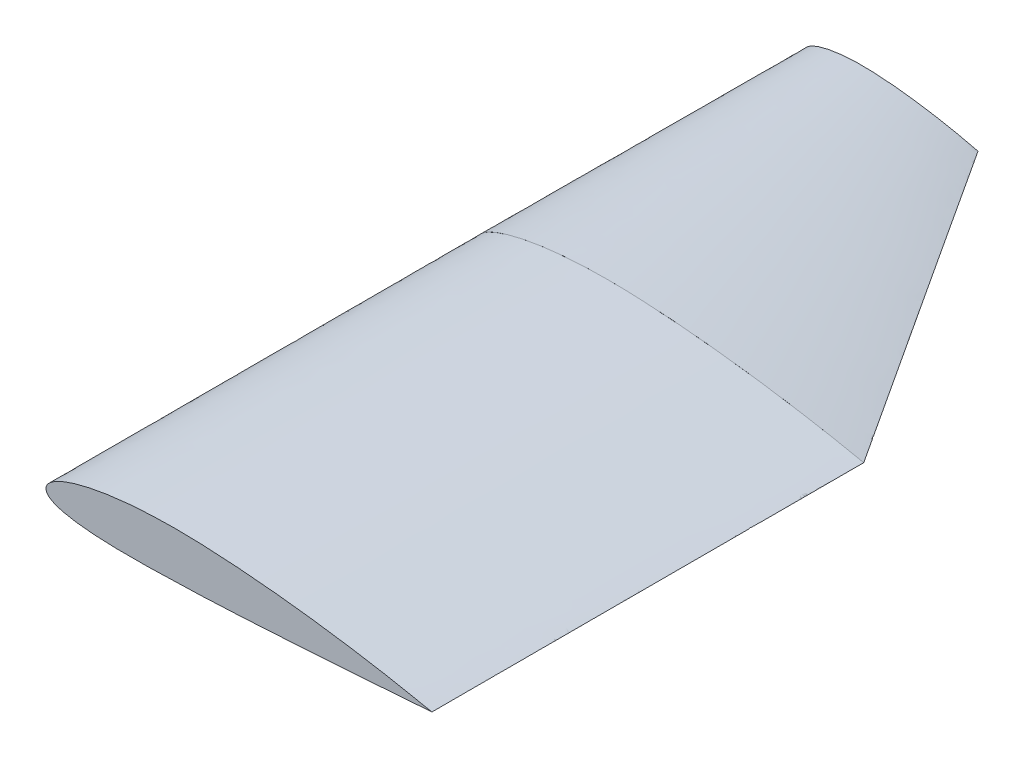
SolidWorks part; units mm, degrees
ref_plane "Front Plane" through (0, 0, 0) normal (0, 0, 1) x (1, 0, 0)
ref_plane "Top Plane" through (0, 0, 0) normal (0, 1, 0) x (1, 0, 0)
ref_plane "Right Plane" through (0, 0, 0) normal (1, 0, 0) x (0, 0, -1)
curve "Airfoil_curve"
  spline degree 3 poles (411.7817, -0.0157, 0) (412.0536, -0.0023, 0) (411.7836, 0.0347, 0) (411.5641, 0.1099, 0) (411.0101, 0.1971, 0) (410.3301, 0.3578, 0) (409.4199, 0.5405, 0) (408.326, 0.7892, 0) (407.0216, 1.0497, 0) (405.5282, 1.3771, 0) (403.8332, 1.7229, 0) (401.9465, 2.1127, 0) (399.8677, 2.5449, 0) (397.6006, 3.0028, 0) (395.1434, 3.4936, 0) (392.5025, 4.019, 0) (389.6787, 4.5968, 0) (386.6746, 5.1833, 0) (383.4891, 5.7888, 0) (380.1348, 6.4442, 0) (376.6043, 7.112, 0) (372.9076, 7.802, 0) (369.0432, 8.5093, 0) (365.0217, 9.2525, 0) (360.8384, 10.0029, 0) (356.5035, 10.7574, 0) (352.0215, 11.542, 0) (347.3944, 12.3298, 0) (342.6243, 13.1292, 0) (337.7185, 13.9416, 0) (332.6805, 14.7465, 0) (327.5183, 15.5701, 0) (322.2356, 16.3914, 0) (316.8334, 17.1938, 0) (311.3256, 18.0218, 0) (305.7074, 18.8254, 0) (299.9917, 19.6385, 0) (294.1815, 20.4376, 0) (288.2846, 21.2259, 0) (282.3022, 22.0103, 0) (276.241, 22.7644, 0) (270.1077, 23.515, 0) (263.9155, 24.2589, 0) (257.6615, 24.9669, 0) (251.3539, 25.6518, 0) (244.9992, 26.3415, 0) (238.601, 26.9733, 0) (232.171, 27.5935, 0) (225.7154, 28.2001, 0) (219.2373, 28.7506, 0) (212.7452, 29.2999, 0) (206.2443, 29.7927, 0) (199.7414, 30.2674, 0) (193.2446, 30.6967, 0) (186.7574, 31.0835, 0) (180.2877, 31.4458, 0) (173.8445, 31.7696, 0) (167.4205, 32.031, 0) (161.0179, 32.2854, 0) (154.6405, 32.4451, 0) (148.3071, 32.5705, 0) (142.0301, 32.6306, 0) (135.8166, 32.6263, 0) (129.6728, 32.5849, 0) (123.6061, 32.4571, 0) (117.6223, 32.2925, 0) (111.7252, 32.0621, 0) (105.9252, 31.7702, 0) (100.2245, 31.434, 0) (94.634, 31.0345, 0) (89.1574, 30.5729, 0) (83.8002, 30.0647, 0) (78.5697, 29.5053, 0) (73.4693, 28.8957, 0) (68.5018, 28.2383, 0) (63.6755, 27.5262, 0) (58.9936, 26.7811, 0) (54.4673, 25.9796, 0) (50.0931, 25.1409, 0) (45.88, 24.2608, 0) (41.8276, 23.3555, 0) (37.9479, 22.4045, 0) (34.2417, 21.424, 0) (30.7038, 20.43, 0) (27.352, 19.3887, 0) (24.1794, 18.3333, 0) (21.1983, 17.248, 0) (18.3933, 16.1691, 0) (15.7911, 15.0448, 0) (13.3707, 13.93, 0) (11.152, 12.7922, 0) (9.1264, 11.6418, 0) (7.297, 10.4891, 0) (5.6707, 9.3274, 0) (4.2399, 8.1698, 0) (3.0185, 7.0028, 0) (1.992, 5.8375, 0) (1.1752, 4.6687, 0) (0.563, 3.4965, 0) (0.151, 2.3287, 0) (-0.0419, 1.1579, 0) (-0.0371, -0.0042, 0) (0.1915, -1.1429, 0) (0.607, -2.2544, 0) (1.2396, -3.3208, 0) (2.0755, -4.3427, 0) (3.0896, -5.3391, 0) (4.3178, -6.2756, 0) (5.7295, -7.1839, 0) (7.3412, -8.0509, 0) (9.1362, -8.8886, 0) (11.1275, -9.6726, 0) (13.2979, -10.4337, 0) (15.6581, -11.1486, 0) (18.197, -11.8252, 0) (20.9146, -12.4663, 0) (23.81, -13.0612, 0) (26.8808, -13.6211, 0) (30.1228, -14.1355, 0) (33.5284, -14.6301, 0) (37.1001, -15.0653, 0) (40.8312, -15.4611, 0) (44.7171, -15.8372, 0) (48.762, -16.1485, 0) (52.9517, -16.4426, 0) (57.2891, -16.6865, 0) (61.762, -16.9145, 0) (66.3764, -17.0724, 0) (71.1193, -17.2298, 0) (75.993, -17.3388, 0) (80.9899, -17.4016, 0) (86.1065, -17.459, 0) (91.3367, -17.4646, 0) (96.6734, -17.4422, 0) (102.1135, -17.4051, 0) (107.6536, -17.3344, 0) (113.2902, -17.2328, 0) (119.0167, -17.1091, 0) (124.8271, -16.9857, 0) (130.7136, -16.8221, 0) (136.6734, -16.6394, 0) (142.7003, -16.4538, 0) (148.7901, -16.2395, 0) (154.9369, -16.0221, 0) (161.1399, -15.7864, 0) (167.4073, -15.5657, 0) (173.7271, -15.3028, 0) (180.0935, -15.0195, 0) (186.4839, -14.7345, 0) (192.8969, -14.4205, 0) (199.3235, -14.1009, 0) (205.7606, -13.7742, 0) (212.197, -13.422, 0) (218.6266, -13.0592, 0) (225.047, -12.7027, 0) (231.4503, -12.3319, 0) (237.8305, -11.9545, 0) (244.1795, -11.5556, 0) (250.4943, -11.189, 0) (256.7663, -10.7768, 0) (262.9901, -10.3923, 0) (269.1639, -10.0047, 0) (275.2731, -9.5993, 0) (281.3169, -9.2129, 0) (287.2869, -8.823, 0) (293.1797, -8.4293, 0) (298.9907, -8.0571, 0) (304.7065, -7.6606, 0) (310.3298, -7.2807, 0) (315.8504, -6.9156, 0) (321.2664, -6.54, 0) (326.5671, -6.186, 0) (331.7532, -5.8214, 0) (336.8133, -5.4725, 0) (341.7504, -5.1361, 0) (346.5495, -4.7894, 0) (351.2138, -4.4768, 0) (355.7333, -4.1526, 0) (360.1067, -3.8433, 0) (364.3305, -3.5473, 0) (368.3962, -3.2406, 0) (372.3035, -2.9653, 0) (376.0434, -2.6944, 0) (379.6167, -2.4337, 0) (383.0202, -2.1862, 0) (386.2496, -1.9409, 0) (389.2974, -1.7296, 0) (392.163, -1.5022, 0) (394.8463, -1.3021, 0) (397.3441, -1.1302, 0) (399.6496, -0.9413, 0) (401.7637, -0.7874, 0) (403.6831, -0.6345, 0) (405.403, -0.5019, 0) (406.9273, -0.4009, 0) (408.25, -0.2803, 0) (409.3715, -0.2065, 0) (410.2993, -0.1365, 0) (410.9956, -0.0759, 0) (411.5538, -0.0325, 0) (411.7817, -0.0157, 0) (412.0536, -0.0023, 0) (411.7836, 0.0347, 0) knots -0.001097 -0.000489 -0.000119 0 0.000121 0.000487 0.001105 0.001956 0.00305 0.004388 0.005967 0.00779 0.009842 0.012136 0.014661 0.017415 0.020385 0.023598 0.027019 0.030665 0.034515 0.038583 0.042855 0.047329 0.051995 0.056866 0.061915 0.067153 0.072559 0.078143 0.083893 0.089809 0.095878 0.102089 0.108454 0.114945 0.121568 0.128318 0.135186 0.142159 0.149235 0.156405 0.163678 0.17102 0.178443 0.185921 0.193467 0.201071 0.208718 0.216398 0.224111 0.231843 0.239585 0.247348 0.255095 0.26284 0.270569 0.278273 0.28595 0.293578 0.301204 0.308803 0.31633 0.323796 0.331191 0.33849 0.345708 0.352832 0.35984 0.366756 0.373544 0.380207 0.386745 0.393146 0.399399 0.405505 0.411465 0.417269 0.422904 0.428373 0.433663 0.438788 0.443723 0.448472 0.453034 0.457396 0.461577 0.465551 0.469319 0.472891 0.476268 0.479427 0.482394 0.485157 0.487733 0.490102 0.492282 0.494291 0.49612 0.497812 0.499364 0.500823 0.502209 0.503576 0.504945 0.506329 0.507789 0.509345 0.511026 0.512848 0.514843 0.517008 0.51937 0.521904 0.524637 0.527571 0.530697 0.534007 0.537528 0.541238 0.545139 0.549235 0.553511 0.557971 0.562616 0.567434 0.572439 0.577596 0.582928 0.588412 0.594062 0.599853 0.605798 0.611885 0.618103 0.624451 0.630919 0.637506 0.644212 0.651025 0.657934 0.664939 0.672028 0.6792 0.686445 0.693761 0.701137 0.708584 0.716128 0.723696 0.731312 0.738942 0.746596 0.754262 0.761929 0.769585 0.77723 0.784863 0.792461 0.800025 0.807552 0.815021 0.822442 0.829792 0.837083 0.844279 0.851391 0.858421 0.865343 0.872159 0.878855 0.885444 0.891891 0.898218 0.904391 0.910433 0.916308 0.922041 0.927594 0.932981 0.938201 0.943231 0.948082 0.952743 0.957201 0.961456 0.965521 0.969371 0.973007 0.976417 0.979624 0.982604 0.985346 0.987874 0.990163 0.992214 0.994026 0.995612 0.996947 0.998044 0.998903 0.999511 0.999881 1 1.000121 1.000487 1.001105 periodic
ref_plane "Panel break" through (0, 0, 461) normal (0, 0, 1) x (1, 0, 0)
sketch "panel 1 root " plane through (0, 0, 0) normal (0, 0, 1) x (1, 0, 0)
  spline S0 degree 3 poles (411.7817, -0.0157) (412.0536, -0.0023) (411.7836, 0.0347) (411.5641, 0.1099) (411.0101, 0.1971) (410.3301, 0.3578) (409.4199, 0.5405) (408.326, 0.7892) (407.0216, 1.0497) (405.5282, 1.3771) (403.8332, 1.7229) (401.9465, 2.1127) (399.8677, 2.5449) (397.6006, 3.0028) (395.1434, 3.4936) (392.5025, 4.019) (389.6787, 4.5968) (386.6746, 5.1833) (383.4891, 5.7888) (380.1348, 6.4442) (376.6043, 7.112) (372.9076, 7.802) (369.0432, 8.5093) (365.0217, 9.2525) (360.8384, 10.0029) (356.5035, 10.7574) (352.0215, 11.542) (347.3944, 12.3298) (342.6243, 13.1292) (337.7185, 13.9416) (332.6805, 14.7465) (327.5183, 15.5701) (322.2356, 16.3914) (316.8334, 17.1938) (311.3256, 18.0218) (305.7074, 18.8254) (299.9917, 19.6385) (294.1815, 20.4376) (288.2846, 21.2259) (282.3022, 22.0103) (276.241, 22.7644) (270.1077, 23.515) (263.9155, 24.2589) (257.6615, 24.9669) (251.3539, 25.6518) (244.9992, 26.3415) (238.601, 26.9733) (232.171, 27.5935) (225.7154, 28.2001) (219.2373, 28.7506) (212.7452, 29.2999) (206.2443, 29.7927) (199.7414, 30.2674) (193.2446, 30.6967) (186.7574, 31.0835) (180.2877, 31.4458) (173.8445, 31.7696) (167.4205, 32.031) (161.0179, 32.2854) (154.6405, 32.4451) (148.3071, 32.5705) (142.0301, 32.6306) (135.8166, 32.6263) (129.6728, 32.5849) (123.6061, 32.4571) (117.6223, 32.2925) (111.7252, 32.0621) (105.9252, 31.7702) (100.2245, 31.434) (94.634, 31.0345) (89.1574, 30.5729) (83.8002, 30.0647) (78.5697, 29.5053) (73.4693, 28.8957) (68.5018, 28.2383) (63.6755, 27.5262) (58.9936, 26.7811) (54.4673, 25.9796) (50.0931, 25.1409) (45.88, 24.2608) (41.8276, 23.3555) (37.9479, 22.4045) (34.2417, 21.424) (30.7038, 20.43) (27.352, 19.3887) (24.1794, 18.3333) (21.1983, 17.248) (18.3933, 16.1691) (15.7911, 15.0448) (13.3707, 13.93) (11.152, 12.7922) (9.1264, 11.6418) (7.297, 10.4891) (5.6707, 9.3274) (4.2399, 8.1698) (3.0185, 7.0028) (1.992, 5.8375) (1.1752, 4.6687) (0.563, 3.4965) (0.151, 2.3287) (-0.0419, 1.1579) (-0.0371, -0.0042) (0.1915, -1.1429) (0.607, -2.2544) (1.2396, -3.3208) (2.0755, -4.3427) (3.0896, -5.3391) (4.3178, -6.2756) (5.7295, -7.1839) (7.3412, -8.0509) (9.1362, -8.8886) (11.1275, -9.6726) (13.2979, -10.4337) (15.6581, -11.1486) (18.197, -11.8252) (20.9146, -12.4663) (23.81, -13.0612) (26.8808, -13.6211) (30.1228, -14.1355) (33.5284, -14.6301) (37.1001, -15.0653) (40.8312, -15.4611) (44.7171, -15.8372) (48.762, -16.1485) (52.9517, -16.4426) (57.2891, -16.6865) (61.762, -16.9145) (66.3764, -17.0724) (71.1193, -17.2298) (75.993, -17.3388) (80.9899, -17.4016) (86.1065, -17.459) (91.3367, -17.4646) (96.6734, -17.4422) (102.1135, -17.4051) (107.6536, -17.3344) (113.2902, -17.2328) (119.0167, -17.1091) (124.8271, -16.9857) (130.7136, -16.8221) (136.6734, -16.6394) (142.7003, -16.4538) (148.7901, -16.2395) (154.9369, -16.0221) (161.1399, -15.7864) (167.4073, -15.5657) (173.7271, -15.3028) (180.0935, -15.0195) (186.4839, -14.7345) (192.8969, -14.4205) (199.3235, -14.1009) (205.7606, -13.7742) (212.197, -13.422) (218.6266, -13.0592) (225.047, -12.7027) (231.4503, -12.3319) (237.8305, -11.9545) (244.1795, -11.5556) (250.4943, -11.189) (256.7663, -10.7768) (262.9901, -10.3923) (269.1639, -10.0047) (275.2731, -9.5993) (281.3169, -9.2129) (287.2869, -8.823) (293.1797, -8.4293) (298.9907, -8.0571) (304.7065, -7.6606) (310.3298, -7.2807) (315.8504, -6.9156) (321.2664, -6.54) (326.5671, -6.186) (331.7532, -5.8214) (336.8133, -5.4725) (341.7504, -5.1361) (346.5495, -4.7894) (351.2138, -4.4768) (355.7333, -4.1526) (360.1067, -3.8433) (364.3305, -3.5473) (368.3962, -3.2406) (372.3035, -2.9653) (376.0434, -2.6944) (379.6167, -2.4337) (383.0202, -2.1862) (386.2496, -1.9409) (389.2974, -1.7296) (392.163, -1.5022) (394.8463, -1.3021) (397.3441, -1.1302) (399.6496, -0.9413) (401.7637, -0.7874) (403.6831, -0.6345) (405.403, -0.5019) (406.9273, -0.4009) (408.25, -0.2803) (409.3715, -0.2065) (410.2993, -0.1365) (410.9956, -0.0759) (411.5538, -0.0325) (411.7817, -0.0157) (412.0536, -0.0023) (411.7836, 0.0347) knots -0.001097 -0.000489 -0.000119 0 0.000121 0.000487 0.001105 0.001956 0.00305 0.004388 0.005967 0.00779 0.009842 0.012136 0.014661 0.017415 0.020385 0.023598 0.027019 0.030665 0.034515 0.038583 0.042855 0.047329 0.051995 0.056866 0.061915 0.067153 0.072559 0.078143 0.083893 0.089809 0.095878 0.102089 0.108454 0.114945 0.121568 0.128318 0.135186 0.142159 0.149235 0.156405 0.163678 0.17102 0.178443 0.185921 0.193467 0.201071 0.208718 0.216398 0.224111 0.231843 0.239585 0.247348 0.255095 0.26284 0.270569 0.278273 0.28595 0.293578 0.301204 0.308803 0.31633 0.323796 0.331191 0.33849 0.345708 0.352832 0.35984 0.366756 0.373544 0.380207 0.386745 0.393146 0.399399 0.405505 0.411465 0.417269 0.422904 0.428373 0.433663 0.438788 0.443723 0.448472 0.453034 0.457396 0.461577 0.465551 0.469319 0.472891 0.476268 0.479427 0.482394 0.485157 0.487733 0.490102 0.492282 0.494291 0.49612 0.497812 0.499364 0.500823 0.502209 0.503576 0.504945 0.506329 0.507789 0.509345 0.511026 0.512848 0.514843 0.517008 0.51937 0.521904 0.524637 0.527571 0.530697 0.534007 0.537528 0.541238 0.545139 0.549235 0.553511 0.557971 0.562616 0.567434 0.572439 0.577596 0.582928 0.588412 0.594062 0.599853 0.605798 0.611885 0.618103 0.624451 0.630919 0.637506 0.644212 0.651025 0.657934 0.664939 0.672028 0.6792 0.686445 0.693761 0.701137 0.708584 0.716128 0.723696 0.731312 0.738942 0.746596 0.754262 0.761929 0.769585 0.77723 0.784863 0.792461 0.800025 0.807552 0.815021 0.822442 0.829792 0.837083 0.844279 0.851391 0.858421 0.865343 0.872159 0.878855 0.885444 0.891891 0.898218 0.904391 0.910433 0.916308 0.922041 0.927594 0.932981 0.938201 0.943231 0.948082 0.952743 0.957201 0.961456 0.965521 0.969371 0.973007 0.976417 0.979624 0.982604 0.985346 0.987874 0.990163 0.992214 0.994026 0.995612 0.996947 0.998044 0.998903 0.999511 0.999881 1 1.000121 1.000487 1.001105 only from (412, 0) to (412, 0) construction
  spline S1 degree 3 poles (411.7817, -0.0157) (412.0536, -0.0023) (411.7836, 0.0347) (411.5641, 0.1099) (411.0101, 0.1971) (410.3301, 0.3578) (409.4199, 0.5405) (408.326, 0.7892) (407.0216, 1.0497) (405.5282, 1.3771) (403.8332, 1.7229) (401.9465, 2.1127) (399.8677, 2.5449) (397.6006, 3.0028) (395.1434, 3.4936) (392.5025, 4.019) (389.6787, 4.5968) (386.6746, 5.1833) (383.4891, 5.7888) (380.1348, 6.4442) (376.6043, 7.112) (372.9076, 7.802) (369.0432, 8.5093) (365.0217, 9.2525) (360.8384, 10.0029) (356.5035, 10.7574) (352.0215, 11.542) (347.3944, 12.3298) (342.6243, 13.1292) (337.7185, 13.9416) (332.6805, 14.7465) (327.5183, 15.5701) (322.2356, 16.3914) (316.8334, 17.1938) (311.3256, 18.0218) (305.7074, 18.8254) (299.9917, 19.6385) (294.1815, 20.4376) (288.2846, 21.2259) (282.3022, 22.0103) (276.241, 22.7644) (270.1077, 23.515) (263.9155, 24.2589) (257.6615, 24.9669) (251.3539, 25.6518) (244.9992, 26.3415) (238.601, 26.9733) (232.171, 27.5935) (225.7154, 28.2001) (219.2373, 28.7506) (212.7452, 29.2999) (206.2443, 29.7927) (199.7414, 30.2674) (193.2446, 30.6967) (186.7574, 31.0835) (180.2877, 31.4458) (173.8445, 31.7696) (167.4205, 32.031) (161.0179, 32.2854) (154.6405, 32.4451) (148.3071, 32.5705) (142.0301, 32.6306) (135.8166, 32.6263) (129.6728, 32.5849) (123.6061, 32.4571) (117.6223, 32.2925) (111.7252, 32.0621) (105.9252, 31.7702) (100.2245, 31.434) (94.634, 31.0345) (89.1574, 30.5729) (83.8002, 30.0647) (78.5697, 29.5053) (73.4693, 28.8957) (68.5018, 28.2383) (63.6755, 27.5262) (58.9936, 26.7811) (54.4673, 25.9796) (50.0931, 25.1409) (45.88, 24.2608) (41.8276, 23.3555) (37.9479, 22.4045) (34.2417, 21.424) (30.7038, 20.43) (27.352, 19.3887) (24.1794, 18.3333) (21.1983, 17.248) (18.3933, 16.1691) (15.7911, 15.0448) (13.3707, 13.93) (11.152, 12.7922) (9.1264, 11.6418) (7.297, 10.4891) (5.6707, 9.3274) (4.2399, 8.1698) (3.0185, 7.0028) (1.992, 5.8375) (1.1752, 4.6687) (0.563, 3.4965) (0.151, 2.3287) (-0.0419, 1.1579) (-0.0371, -0.0042) (0.1915, -1.1429) (0.607, -2.2544) (1.2396, -3.3208) (2.0755, -4.3427) (3.0896, -5.3391) (4.3178, -6.2756) (5.7295, -7.1839) (7.3412, -8.0509) (9.1362, -8.8886) (11.1275, -9.6726) (13.2979, -10.4337) (15.6581, -11.1486) (18.197, -11.8252) (20.9146, -12.4663) (23.81, -13.0612) (26.8808, -13.6211) (30.1228, -14.1355) (33.5284, -14.6301) (37.1001, -15.0653) (40.8312, -15.4611) (44.7171, -15.8372) (48.762, -16.1485) (52.9517, -16.4426) (57.2891, -16.6865) (61.762, -16.9145) (66.3764, -17.0724) (71.1193, -17.2298) (75.993, -17.3388) (80.9899, -17.4016) (86.1065, -17.459) (91.3367, -17.4646) (96.6734, -17.4422) (102.1135, -17.4051) (107.6536, -17.3344) (113.2902, -17.2328) (119.0167, -17.1091) (124.8271, -16.9857) (130.7136, -16.8221) (136.6734, -16.6394) (142.7003, -16.4538) (148.7901, -16.2395) (154.9369, -16.0221) (161.1399, -15.7864) (167.4073, -15.5657) (173.7271, -15.3028) (180.0935, -15.0195) (186.4839, -14.7345) (192.8969, -14.4205) (199.3235, -14.1009) (205.7606, -13.7742) (212.197, -13.422) (218.6266, -13.0592) (225.047, -12.7027) (231.4503, -12.3319) (237.8305, -11.9545) (244.1795, -11.5556) (250.4943, -11.189) (256.7663, -10.7768) (262.9901, -10.3923) (269.1639, -10.0047) (275.2731, -9.5993) (281.3169, -9.2129) (287.2869, -8.823) (293.1797, -8.4293) (298.9907, -8.0571) (304.7065, -7.6606) (310.3298, -7.2807) (315.8504, -6.9156) (321.2664, -6.54) (326.5671, -6.186) (331.7532, -5.8214) (336.8133, -5.4725) (341.7504, -5.1361) (346.5495, -4.7894) (351.2138, -4.4768) (355.7333, -4.1526) (360.1067, -3.8433) (364.3305, -3.5473) (368.3962, -3.2406) (372.3035, -2.9653) (376.0434, -2.6944) (379.6167, -2.4337) (383.0202, -2.1862) (386.2496, -1.9409) (389.2974, -1.7296) (392.163, -1.5022) (394.8463, -1.3021) (397.3441, -1.1302) (399.6496, -0.9413) (401.7637, -0.7874) (403.6831, -0.6345) (405.403, -0.5019) (406.9273, -0.4009) (408.25, -0.2803) (409.3715, -0.2065) (410.2993, -0.1365) (410.9956, -0.0759) (411.5538, -0.0325) (411.7817, -0.0157) (412.0536, -0.0023) (411.7836, 0.0347) knots -0.001097 -0.000489 -0.000119 0 0.000121 0.000487 0.001105 0.001956 0.00305 0.004388 0.005967 0.00779 0.009842 0.012136 0.014661 0.017415 0.020385 0.023598 0.027019 0.030665 0.034515 0.038583 0.042855 0.047329 0.051995 0.056866 0.061915 0.067153 0.072559 0.078143 0.083893 0.089809 0.095878 0.102089 0.108454 0.114945 0.121568 0.128318 0.135186 0.142159 0.149235 0.156405 0.163678 0.17102 0.178443 0.185921 0.193467 0.201071 0.208718 0.216398 0.224111 0.231843 0.239585 0.247348 0.255095 0.26284 0.270569 0.278273 0.28595 0.293578 0.301204 0.308803 0.31633 0.323796 0.331191 0.33849 0.345708 0.352832 0.35984 0.366756 0.373544 0.380207 0.386745 0.393146 0.399399 0.405505 0.411465 0.417269 0.422904 0.428373 0.433663 0.438788 0.443723 0.448472 0.453034 0.457396 0.461577 0.465551 0.469319 0.472891 0.476268 0.479427 0.482394 0.485157 0.487733 0.490102 0.492282 0.494291 0.49612 0.497812 0.499364 0.500823 0.502209 0.503576 0.504945 0.506329 0.507789 0.509345 0.511026 0.512848 0.514843 0.517008 0.51937 0.521904 0.524637 0.527571 0.530697 0.534007 0.537528 0.541238 0.545139 0.549235 0.553511 0.557971 0.562616 0.567434 0.572439 0.577596 0.582928 0.588412 0.594062 0.599853 0.605798 0.611885 0.618103 0.624451 0.630919 0.637506 0.644212 0.651025 0.657934 0.664939 0.672028 0.6792 0.686445 0.693761 0.701137 0.708584 0.716128 0.723696 0.731312 0.738942 0.746596 0.754262 0.761929 0.769585 0.77723 0.784863 0.792461 0.800025 0.807552 0.815021 0.822442 0.829792 0.837083 0.844279 0.851391 0.858421 0.865343 0.872159 0.878855 0.885444 0.891891 0.898218 0.904391 0.910433 0.916308 0.922041 0.927594 0.932981 0.938201 0.943231 0.948082 0.952743 0.957201 0.961456 0.965521 0.969371 0.973007 0.976417 0.979624 0.982604 0.985346 0.987874 0.990163 0.992214 0.994026 0.995612 0.996947 0.998044 0.998903 0.999511 0.999881 1 1.000121 1.000487 1.001105 only from (412, 0) to (412, 0)
sketch "panel 2 root " plane through (0, 0, 461) normal (0, 0, 1) x (1, 0, 0)
  spline S0 degree 3 poles (411.7817, -0.0157) (412.0536, -0.0023) (411.7836, 0.0347) (411.5641, 0.1099) (411.0101, 0.1971) (410.3301, 0.3578) (409.4199, 0.5405) (408.326, 0.7892) (407.0216, 1.0497) (405.5282, 1.3771) (403.8332, 1.7229) (401.9465, 2.1127) (399.8677, 2.5449) (397.6006, 3.0028) (395.1434, 3.4936) (392.5025, 4.019) (389.6787, 4.5968) (386.6746, 5.1833) (383.4891, 5.7888) (380.1348, 6.4442) (376.6043, 7.112) (372.9076, 7.802) (369.0432, 8.5093) (365.0217, 9.2525) (360.8384, 10.0029) (356.5035, 10.7574) (352.0215, 11.542) (347.3944, 12.3298) (342.6243, 13.1292) (337.7185, 13.9416) (332.6805, 14.7465) (327.5183, 15.5701) (322.2356, 16.3914) (316.8334, 17.1938) (311.3256, 18.0218) (305.7074, 18.8254) (299.9917, 19.6385) (294.1815, 20.4376) (288.2846, 21.2259) (282.3022, 22.0103) (276.241, 22.7644) (270.1077, 23.515) (263.9155, 24.2589) (257.6615, 24.9669) (251.3539, 25.6518) (244.9992, 26.3415) (238.601, 26.9733) (232.171, 27.5935) (225.7154, 28.2001) (219.2373, 28.7506) (212.7452, 29.2999) (206.2443, 29.7927) (199.7414, 30.2674) (193.2446, 30.6967) (186.7574, 31.0835) (180.2877, 31.4458) (173.8445, 31.7696) (167.4205, 32.031) (161.0179, 32.2854) (154.6405, 32.4451) (148.3071, 32.5705) (142.0301, 32.6306) (135.8166, 32.6263) (129.6728, 32.5849) (123.6061, 32.4571) (117.6223, 32.2925) (111.7252, 32.0621) (105.9252, 31.7702) (100.2245, 31.434) (94.634, 31.0345) (89.1574, 30.5729) (83.8002, 30.0647) (78.5697, 29.5053) (73.4693, 28.8957) (68.5018, 28.2383) (63.6755, 27.5262) (58.9936, 26.7811) (54.4673, 25.9796) (50.0931, 25.1409) (45.88, 24.2608) (41.8276, 23.3555) (37.9479, 22.4045) (34.2417, 21.424) (30.7038, 20.43) (27.352, 19.3887) (24.1794, 18.3333) (21.1983, 17.248) (18.3933, 16.1691) (15.7911, 15.0448) (13.3707, 13.93) (11.152, 12.7922) (9.1264, 11.6418) (7.297, 10.4891) (5.6707, 9.3274) (4.2399, 8.1698) (3.0185, 7.0028) (1.992, 5.8375) (1.1752, 4.6687) (0.563, 3.4965) (0.151, 2.3287) (-0.0419, 1.1579) (-0.0371, -0.0042) (0.1915, -1.1429) (0.607, -2.2544) (1.2396, -3.3208) (2.0755, -4.3427) (3.0896, -5.3391) (4.3178, -6.2756) (5.7295, -7.1839) (7.3412, -8.0509) (9.1362, -8.8886) (11.1275, -9.6726) (13.2979, -10.4337) (15.6581, -11.1486) (18.197, -11.8252) (20.9146, -12.4663) (23.81, -13.0612) (26.8808, -13.6211) (30.1228, -14.1355) (33.5284, -14.6301) (37.1001, -15.0653) (40.8312, -15.4611) (44.7171, -15.8372) (48.762, -16.1485) (52.9517, -16.4426) (57.2891, -16.6865) (61.762, -16.9145) (66.3764, -17.0724) (71.1193, -17.2298) (75.993, -17.3388) (80.9899, -17.4016) (86.1065, -17.459) (91.3367, -17.4646) (96.6734, -17.4422) (102.1135, -17.4051) (107.6536, -17.3344) (113.2902, -17.2328) (119.0167, -17.1091) (124.8271, -16.9857) (130.7136, -16.8221) (136.6734, -16.6394) (142.7003, -16.4538) (148.7901, -16.2395) (154.9369, -16.0221) (161.1399, -15.7864) (167.4073, -15.5657) (173.7271, -15.3028) (180.0935, -15.0195) (186.4839, -14.7345) (192.8969, -14.4205) (199.3235, -14.1009) (205.7606, -13.7742) (212.197, -13.422) (218.6266, -13.0592) (225.047, -12.7027) (231.4503, -12.3319) (237.8305, -11.9545) (244.1795, -11.5556) (250.4943, -11.189) (256.7663, -10.7768) (262.9901, -10.3923) (269.1639, -10.0047) (275.2731, -9.5993) (281.3169, -9.2129) (287.2869, -8.823) (293.1797, -8.4293) (298.9907, -8.0571) (304.7065, -7.6606) (310.3298, -7.2807) (315.8504, -6.9156) (321.2664, -6.54) (326.5671, -6.186) (331.7532, -5.8214) (336.8133, -5.4725) (341.7504, -5.1361) (346.5495, -4.7894) (351.2138, -4.4768) (355.7333, -4.1526) (360.1067, -3.8433) (364.3305, -3.5473) (368.3962, -3.2406) (372.3035, -2.9653) (376.0434, -2.6944) (379.6167, -2.4337) (383.0202, -2.1862) (386.2496, -1.9409) (389.2974, -1.7296) (392.163, -1.5022) (394.8463, -1.3021) (397.3441, -1.1302) (399.6496, -0.9413) (401.7637, -0.7874) (403.6831, -0.6345) (405.403, -0.5019) (406.9273, -0.4009) (408.25, -0.2803) (409.3715, -0.2065) (410.2993, -0.1365) (410.9956, -0.0759) (411.5538, -0.0325) (411.7817, -0.0157) (412.0536, -0.0023) (411.7836, 0.0347) knots -0.001097 -0.000489 -0.000119 0 0.000121 0.000487 0.001105 0.001956 0.00305 0.004388 0.005967 0.00779 0.009842 0.012136 0.014661 0.017415 0.020385 0.023598 0.027019 0.030665 0.034515 0.038583 0.042855 0.047329 0.051995 0.056866 0.061915 0.067153 0.072559 0.078143 0.083893 0.089809 0.095878 0.102089 0.108454 0.114945 0.121568 0.128318 0.135186 0.142159 0.149235 0.156405 0.163678 0.17102 0.178443 0.185921 0.193467 0.201071 0.208718 0.216398 0.224111 0.231843 0.239585 0.247348 0.255095 0.26284 0.270569 0.278273 0.28595 0.293578 0.301204 0.308803 0.31633 0.323796 0.331191 0.33849 0.345708 0.352832 0.35984 0.366756 0.373544 0.380207 0.386745 0.393146 0.399399 0.405505 0.411465 0.417269 0.422904 0.428373 0.433663 0.438788 0.443723 0.448472 0.453034 0.457396 0.461577 0.465551 0.469319 0.472891 0.476268 0.479427 0.482394 0.485157 0.487733 0.490102 0.492282 0.494291 0.49612 0.497812 0.499364 0.500823 0.502209 0.503576 0.504945 0.506329 0.507789 0.509345 0.511026 0.512848 0.514843 0.517008 0.51937 0.521904 0.524637 0.527571 0.530697 0.534007 0.537528 0.541238 0.545139 0.549235 0.553511 0.557971 0.562616 0.567434 0.572439 0.577596 0.582928 0.588412 0.594062 0.599853 0.605798 0.611885 0.618103 0.624451 0.630919 0.637506 0.644212 0.651025 0.657934 0.664939 0.672028 0.6792 0.686445 0.693761 0.701137 0.708584 0.716128 0.723696 0.731312 0.738942 0.746596 0.754262 0.761929 0.769585 0.77723 0.784863 0.792461 0.800025 0.807552 0.815021 0.822442 0.829792 0.837083 0.844279 0.851391 0.858421 0.865343 0.872159 0.878855 0.885444 0.891891 0.898218 0.904391 0.910433 0.916308 0.922041 0.927594 0.932981 0.938201 0.943231 0.948082 0.952743 0.957201 0.961456 0.965521 0.969371 0.973007 0.976417 0.979624 0.982604 0.985346 0.987874 0.990163 0.992214 0.994026 0.995612 0.996947 0.998044 0.998903 0.999511 0.999881 1 1.000121 1.000487 1.001105 only from (412, 0) to (412, 0) construction
  spline S1 degree 3 poles (411.7817, -0.0157) (412.0536, -0.0023) (411.7836, 0.0347) (411.5641, 0.1099) (411.0101, 0.1971) (410.3301, 0.3578) (409.4199, 0.5405) (408.326, 0.7892) (407.0216, 1.0497) (405.5282, 1.3771) (403.8332, 1.7229) (401.9465, 2.1127) (399.8677, 2.5449) (397.6006, 3.0028) (395.1434, 3.4936) (392.5025, 4.019) (389.6787, 4.5968) (386.6746, 5.1833) (383.4891, 5.7888) (380.1348, 6.4442) (376.6043, 7.112) (372.9076, 7.802) (369.0432, 8.5093) (365.0217, 9.2525) (360.8384, 10.0029) (356.5035, 10.7574) (352.0215, 11.542) (347.3944, 12.3298) (342.6243, 13.1292) (337.7185, 13.9416) (332.6805, 14.7465) (327.5183, 15.5701) (322.2356, 16.3914) (316.8334, 17.1938) (311.3256, 18.0218) (305.7074, 18.8254) (299.9917, 19.6385) (294.1815, 20.4376) (288.2846, 21.2259) (282.3022, 22.0103) (276.241, 22.7644) (270.1077, 23.515) (263.9155, 24.2589) (257.6615, 24.9669) (251.3539, 25.6518) (244.9992, 26.3415) (238.601, 26.9733) (232.171, 27.5935) (225.7154, 28.2001) (219.2373, 28.7506) (212.7452, 29.2999) (206.2443, 29.7927) (199.7414, 30.2674) (193.2446, 30.6967) (186.7574, 31.0835) (180.2877, 31.4458) (173.8445, 31.7696) (167.4205, 32.031) (161.0179, 32.2854) (154.6405, 32.4451) (148.3071, 32.5705) (142.0301, 32.6306) (135.8166, 32.6263) (129.6728, 32.5849) (123.6061, 32.4571) (117.6223, 32.2925) (111.7252, 32.0621) (105.9252, 31.7702) (100.2245, 31.434) (94.634, 31.0345) (89.1574, 30.5729) (83.8002, 30.0647) (78.5697, 29.5053) (73.4693, 28.8957) (68.5018, 28.2383) (63.6755, 27.5262) (58.9936, 26.7811) (54.4673, 25.9796) (50.0931, 25.1409) (45.88, 24.2608) (41.8276, 23.3555) (37.9479, 22.4045) (34.2417, 21.424) (30.7038, 20.43) (27.352, 19.3887) (24.1794, 18.3333) (21.1983, 17.248) (18.3933, 16.1691) (15.7911, 15.0448) (13.3707, 13.93) (11.152, 12.7922) (9.1264, 11.6418) (7.297, 10.4891) (5.6707, 9.3274) (4.2399, 8.1698) (3.0185, 7.0028) (1.992, 5.8375) (1.1752, 4.6687) (0.563, 3.4965) (0.151, 2.3287) (-0.0419, 1.1579) (-0.0371, -0.0042) (0.1915, -1.1429) (0.607, -2.2544) (1.2396, -3.3208) (2.0755, -4.3427) (3.0896, -5.3391) (4.3178, -6.2756) (5.7295, -7.1839) (7.3412, -8.0509) (9.1362, -8.8886) (11.1275, -9.6726) (13.2979, -10.4337) (15.6581, -11.1486) (18.197, -11.8252) (20.9146, -12.4663) (23.81, -13.0612) (26.8808, -13.6211) (30.1228, -14.1355) (33.5284, -14.6301) (37.1001, -15.0653) (40.8312, -15.4611) (44.7171, -15.8372) (48.762, -16.1485) (52.9517, -16.4426) (57.2891, -16.6865) (61.762, -16.9145) (66.3764, -17.0724) (71.1193, -17.2298) (75.993, -17.3388) (80.9899, -17.4016) (86.1065, -17.459) (91.3367, -17.4646) (96.6734, -17.4422) (102.1135, -17.4051) (107.6536, -17.3344) (113.2902, -17.2328) (119.0167, -17.1091) (124.8271, -16.9857) (130.7136, -16.8221) (136.6734, -16.6394) (142.7003, -16.4538) (148.7901, -16.2395) (154.9369, -16.0221) (161.1399, -15.7864) (167.4073, -15.5657) (173.7271, -15.3028) (180.0935, -15.0195) (186.4839, -14.7345) (192.8969, -14.4205) (199.3235, -14.1009) (205.7606, -13.7742) (212.197, -13.422) (218.6266, -13.0592) (225.047, -12.7027) (231.4503, -12.3319) (237.8305, -11.9545) (244.1795, -11.5556) (250.4943, -11.189) (256.7663, -10.7768) (262.9901, -10.3923) (269.1639, -10.0047) (275.2731, -9.5993) (281.3169, -9.2129) (287.2869, -8.823) (293.1797, -8.4293) (298.9907, -8.0571) (304.7065, -7.6606) (310.3298, -7.2807) (315.8504, -6.9156) (321.2664, -6.54) (326.5671, -6.186) (331.7532, -5.8214) (336.8133, -5.4725) (341.7504, -5.1361) (346.5495, -4.7894) (351.2138, -4.4768) (355.7333, -4.1526) (360.1067, -3.8433) (364.3305, -3.5473) (368.3962, -3.2406) (372.3035, -2.9653) (376.0434, -2.6944) (379.6167, -2.4337) (383.0202, -2.1862) (386.2496, -1.9409) (389.2974, -1.7296) (392.163, -1.5022) (394.8463, -1.3021) (397.3441, -1.1302) (399.6496, -0.9413) (401.7637, -0.7874) (403.6831, -0.6345) (405.403, -0.5019) (406.9273, -0.4009) (408.25, -0.2803) (409.3715, -0.2065) (410.2993, -0.1365) (410.9956, -0.0759) (411.5538, -0.0325) (411.7817, -0.0157) (412.0536, -0.0023) (411.7836, 0.0347) knots -0.001097 -0.000489 -0.000119 0 0.000121 0.000487 0.001105 0.001956 0.00305 0.004388 0.005967 0.00779 0.009842 0.012136 0.014661 0.017415 0.020385 0.023598 0.027019 0.030665 0.034515 0.038583 0.042855 0.047329 0.051995 0.056866 0.061915 0.067153 0.072559 0.078143 0.083893 0.089809 0.095878 0.102089 0.108454 0.114945 0.121568 0.128318 0.135186 0.142159 0.149235 0.156405 0.163678 0.17102 0.178443 0.185921 0.193467 0.201071 0.208718 0.216398 0.224111 0.231843 0.239585 0.247348 0.255095 0.26284 0.270569 0.278273 0.28595 0.293578 0.301204 0.308803 0.31633 0.323796 0.331191 0.33849 0.345708 0.352832 0.35984 0.366756 0.373544 0.380207 0.386745 0.393146 0.399399 0.405505 0.411465 0.417269 0.422904 0.428373 0.433663 0.438788 0.443723 0.448472 0.453034 0.457396 0.461577 0.465551 0.469319 0.472891 0.476268 0.479427 0.482394 0.485157 0.487733 0.490102 0.492282 0.494291 0.49612 0.497812 0.499364 0.500823 0.502209 0.503576 0.504945 0.506329 0.507789 0.509345 0.511026 0.512848 0.514843 0.517008 0.51937 0.521904 0.524637 0.527571 0.530697 0.534007 0.537528 0.541238 0.545139 0.549235 0.553511 0.557971 0.562616 0.567434 0.572439 0.577596 0.582928 0.588412 0.594062 0.599853 0.605798 0.611885 0.618103 0.624451 0.630919 0.637506 0.644212 0.651025 0.657934 0.664939 0.672028 0.6792 0.686445 0.693761 0.701137 0.708584 0.716128 0.723696 0.731312 0.738942 0.746596 0.754262 0.761929 0.769585 0.77723 0.784863 0.792461 0.800025 0.807552 0.815021 0.822442 0.829792 0.837083 0.844279 0.851391 0.858421 0.865343 0.872159 0.878855 0.885444 0.891891 0.898218 0.904391 0.910433 0.916308 0.922041 0.927594 0.932981 0.938201 0.943231 0.948082 0.952743 0.957201 0.961456 0.965521 0.969371 0.973007 0.976417 0.979624 0.982604 0.985346 0.987874 0.990163 0.992214 0.994026 0.995612 0.996947 0.998044 0.998903 0.999511 0.999881 1 1.000121 1.000487 1.001105 only from (412, 0) to (412, 0)
loft "Loft1" add profiles "panel 2 root ", "panel 1 root " connector at (137.2121, 32.6243, 461) connector at (137.1279, 32.6241, 0)
ref_plane "panel end " through (0, 0, 810) normal (0, 0, 1) x (1, 0, 0)
curve "airfoil tip curve"
  spline degree 3 poles (184.904, -0.0171, 0) (185.027, 0.0005, 0) (184.9007, 0.0138, 0) (184.8037, 0.066, 0) (184.5545, 0.0994, 0) (184.2507, 0.1926, 0) (183.8421, 0.2852, 0) (183.3492, 0.4055, 0) (182.772, 0.5617, 0) (182.0983, 0.7131, 0) (181.3422, 0.9122, 0) (180.4913, 1.1017, 0) (179.565, 1.3402, 0) (178.5499, 1.5761, 0) (177.4503, 1.838, 0) (176.266, 2.1139, 0) (175.0015, 2.4197, 0) (173.6542, 2.7271, 0) (172.2231, 3.0457, 0) (170.7159, 3.3831, 0) (169.1359, 3.7514, 0) (167.4755, 4.1012, 0) (165.7489, 4.4902, 0) (163.9424, 4.8624, 0) (162.0718, 5.2688, 0) (160.1223, 5.6618, 0) (158.1161, 6.0902, 0) (156.0353, 6.4897, 0) (153.8996, 6.9318, 0) (151.6929, 7.3413, 0) (149.4332, 7.7724, 0) (147.1222, 8.2183, 0) (144.751, 8.6454, 0) (142.326, 9.0697, 0) (139.8522, 9.5193, 0) (137.33, 9.9402, 0) (134.7651, 10.3774, 0) (132.157, 10.7922, 0) (129.5071, 11.2129, 0) (126.8211, 11.6341, 0) (124.0979, 12.0447, 0) (121.3441, 12.4423, 0) (118.5579, 12.8357, 0) (115.7464, 13.2081, 0) (112.9119, 13.5977, 0) (110.0571, 13.9502, 0) (107.1848, 14.3059, 0) (104.2939, 14.6321, 0) (101.3905, 14.9511, 0) (98.4778, 15.2642, 0) (95.561, 15.5539, 0) (92.637, 15.8201, 0) (89.7148, 16.087, 0) (86.7902, 16.3099, 0) (83.874, 16.5328, 0) (80.9644, 16.7366, 0) (78.0668, 16.8984, 0) (75.1775, 17.0669, 0) (72.2939, 17.1943, 0) (69.4204, 17.2947, 0) (66.567, 17.3645, 0) (63.7401, 17.4059, 0) (60.94, 17.4113, 0) (58.1698, 17.4088, 0) (55.433, 17.3545, 0) (52.7361, 17.2762, 0) (50.0793, 17.1655, 0) (47.4657, 17.0264, 0) (44.8987, 16.8572, 0) (42.3819, 16.6566, 0) (39.915, 16.427, 0) (37.501, 16.1699, 0) (35.1452, 15.875, 0) (32.8472, 15.5695, 0) (30.61, 15.2305, 0) (28.4405, 14.8589, 0) (26.3372, 14.4677, 0) (24.2986, 14.0625, 0) (22.3324, 13.6214, 0) (20.439, 13.1605, 0) (18.6209, 12.6843, 0) (16.88, 12.1782, 0) (15.2105, 11.6794, 0) (13.6308, 11.1329, 0) (12.128, 10.581, 0) (10.7013, 10.0324, 0) (9.3711, 9.4424, 0) (8.1146, 8.8683, 0) (6.9498, 8.2716, 0) (5.8739, 7.6579, 0) (4.887, 7.0399, 0) (3.9813, 6.4222, 0) (3.1724, 5.7913, 0) (2.4465, 5.1619, 0) (1.8148, 4.5257, 0) (1.2832, 3.8781, 0) (0.8261, 3.2434, 0) (0.4722, 2.5947, 0) (0.2079, 1.948, 0) (0.049, 1.2938, 0) (-0.0382, 0.6459, 0) (-0.0144, -0.0014, 0) (0.0962, -0.6374, 0) (0.2977, -1.2603, 0) (0.5912, -1.8655, 0) (0.9767, -2.4455, 0) (1.4432, -3.0142, 0) (2.0014, -3.5585, 0) (2.6519, -4.0809, 0) (3.3821, -4.591, 0) (4.2005, -5.0794, 0) (5.108, -5.5348, 0) (6.089, -5.9888, 0) (7.1539, -6.4154, 0) (8.3046, -6.8128, 0) (9.5286, -7.2073, 0) (10.8407, -7.5569, 0) (12.2205, -7.9157, 0) (13.6803, -8.2284, 0) (15.2134, -8.5309, 0) (16.8177, -8.8073, 0) (18.4943, -9.0694, 0) (20.2416, -9.3068, 0) (22.0579, -9.5291, 0) (23.9388, -9.7161, 0) (25.8828, -9.8829, 0) (27.8886, -10.049, 0) (29.9561, -10.1734, 0) (32.0827, -10.2862, 0) (34.2665, -10.3705, 0) (36.5061, -10.4576, 0) (38.7965, -10.5035, 0) (41.1366, -10.5307, 0) (43.5233, -10.5552, 0) (45.9567, -10.5491, 0) (48.4335, -10.5484, 0) (50.9566, -10.4962, 0) (53.5202, -10.4645, 0) (56.1203, -10.404, 0) (58.7532, -10.3169, 0) (61.4171, -10.245, 0) (64.1135, -10.1408, 0) (66.8366, -10.0277, 0) (69.5872, -9.9258, 0) (72.3632, -9.7861, 0) (75.1705, -9.6646, 0) (78.0036, -9.5113, 0) (80.8565, -9.3478, 0) (83.724, -9.1947, 0) (86.6003, -9.0117, 0) (89.4799, -8.8182, 0) (92.3642, -8.6354, 0) (95.2499, -8.4186, 0) (98.1367, -8.2102, 0) (101.0171, -8.0023, 0) (103.8871, -7.7824, 0) (106.7467, -7.5501, 0) (109.5966, -7.3196, 0) (112.4306, -7.0943, 0) (115.2466, -6.8495, 0) (118.0401, -6.6116, 0) (120.8101, -6.3713, 0) (123.5534, -6.1307, 0) (126.2668, -5.8919, 0) (128.9468, -5.6518, 0) (131.5901, -5.4113, 0) (134.1968, -5.1716, 0) (136.7669, -4.9329, 0) (139.2929, -4.6886, 0) (141.7743, -4.4665, 0) (144.203, -4.2195, 0) (146.5831, -3.9905, 0) (148.9136, -3.7729, 0) (151.1902, -3.5526, 0) (153.4071, -3.3343, 0) (155.563, -3.1102, 0) (157.6565, -2.9017, 0) (159.6903, -2.7028, 0) (161.6572, -2.5056, 0) (163.5556, -2.2964, 0) (165.3847, -2.1303, 0) (167.1389, -1.9259, 0) (168.824, -1.7667, 0) (170.4331, -1.5908, 0) (171.9639, -1.4353, 0) (173.4133, -1.2735, 0) (174.7824, -1.1179, 0) (176.0747, -0.9996, 0) (177.2792, -0.8496, 0) (178.4032, -0.7322, 0) (179.4408, -0.6271, 0) (180.3892, -0.5092, 0) (181.254, -0.4258, 0) (182.0301, -0.334, 0) (182.7159, -0.2506, 0) (183.3142, -0.1949, 0) (183.8161, -0.1361, 0) (184.2315, -0.078, 0) (184.548, -0.059, 0) (184.7964, -0.0174, 0) (184.904, -0.0171, 0) (185.027, 0.0005, 0) (184.9007, 0.0138, 0) knots -0.001111 -0.000476 -0.000134 0 0.000134 0.000491 0.001109 0.001949 0.003057 0.004382 0.005954 0.007763 0.009819 0.012111 0.014626 0.017352 0.020319 0.023528 0.026928 0.030565 0.034412 0.038475 0.042729 0.047188 0.051838 0.056667 0.061713 0.066913 0.07233 0.077869 0.083599 0.089505 0.095544 0.101717 0.108041 0.114519 0.121105 0.127842 0.134657 0.141597 0.14864 0.155788 0.163009 0.17033 0.1777 0.18517 0.192666 0.200233 0.207823 0.215459 0.223144 0.230827 0.23853 0.246228 0.25395 0.26164 0.269327 0.276984 0.28461 0.292183 0.299777 0.307342 0.314826 0.322256 0.329607 0.336879 0.344073 0.351164 0.358127 0.365014 0.371776 0.378386 0.384898 0.391288 0.397504 0.403596 0.409544 0.415323 0.42093 0.426393 0.431692 0.436798 0.441739 0.446492 0.451076 0.455459 0.459653 0.463685 0.467494 0.471112 0.474563 0.477797 0.480863 0.483732 0.486426 0.488938 0.491295 0.493477 0.495531 0.497446 0.499283 0.501015 0.502734 0.504415 0.506094 0.507805 0.509554 0.511374 0.513277 0.515337 0.517502 0.51984 0.522348 0.525001 0.527832 0.530859 0.534031 0.537418 0.540985 0.544722 0.548646 0.552739 0.557029 0.561466 0.566103 0.570915 0.575876 0.580988 0.586282 0.591726 0.597299 0.603053 0.608938 0.614951 0.621094 0.627369 0.633748 0.640258 0.646875 0.653622 0.660449 0.667357 0.674369 0.681436 0.688608 0.695834 0.703113 0.710498 0.717964 0.725457 0.733003 0.740579 0.748156 0.755733 0.763339 0.770946 0.778527 0.786083 0.793616 0.801122 0.808602 0.816005 0.823383 0.830682 0.837902 0.845071 0.852134 0.859093 0.865974 0.87275 0.879422 0.88596 0.89237 0.898647 0.904791 0.910804 0.916661 0.922334 0.927875 0.93323 0.938428 0.943443 0.948271 0.952892 0.957351 0.961601 0.965639 0.969469 0.973087 0.97649 0.979688 0.982645 0.985391 0.987901 0.990171 0.992232 0.994056 0.995613 0.996961 0.998045 0.998889 0.999524 0.999866 1 1.000134 1.000491 1.001109 periodic
sketch "panel 2 tip " plane through (0, 0, 810) normal (0, 0, 1) x (1, 0, 0)
  spline S0 degree 3 poles (184.904, -0.0171) (185.027, 0.0005) (184.9007, 0.0138) (184.8037, 0.066) (184.5545, 0.0994) (184.2507, 0.1926) (183.8421, 0.2852) (183.3492, 0.4055) (182.772, 0.5617) (182.0983, 0.7131) (181.3422, 0.9122) (180.4913, 1.1017) (179.565, 1.3402) (178.5499, 1.5761) (177.4503, 1.838) (176.266, 2.1139) (175.0015, 2.4197) (173.6542, 2.7271) (172.2231, 3.0457) (170.7159, 3.3831) (169.1359, 3.7514) (167.4755, 4.1012) (165.7489, 4.4902) (163.9424, 4.8624) (162.0718, 5.2688) (160.1223, 5.6618) (158.1161, 6.0902) (156.0353, 6.4897) (153.8996, 6.9318) (151.6929, 7.3413) (149.4332, 7.7724) (147.1222, 8.2183) (144.751, 8.6454) (142.326, 9.0697) (139.8522, 9.5193) (137.33, 9.9402) (134.7651, 10.3774) (132.157, 10.7922) (129.5071, 11.2129) (126.8211, 11.6341) (124.0979, 12.0447) (121.3441, 12.4423) (118.5579, 12.8357) (115.7464, 13.2081) (112.9119, 13.5977) (110.0571, 13.9502) (107.1848, 14.3059) (104.2939, 14.6321) (101.3905, 14.9511) (98.4778, 15.2642) (95.561, 15.5539) (92.637, 15.8201) (89.7148, 16.087) (86.7902, 16.3099) (83.874, 16.5328) (80.9644, 16.7366) (78.0668, 16.8984) (75.1775, 17.0669) (72.2939, 17.1943) (69.4204, 17.2947) (66.567, 17.3645) (63.7401, 17.4059) (60.94, 17.4113) (58.1698, 17.4088) (55.433, 17.3545) (52.7361, 17.2762) (50.0793, 17.1655) (47.4657, 17.0264) (44.8987, 16.8572) (42.3819, 16.6566) (39.915, 16.427) (37.501, 16.1699) (35.1452, 15.875) (32.8472, 15.5695) (30.61, 15.2305) (28.4405, 14.8589) (26.3372, 14.4677) (24.2986, 14.0625) (22.3324, 13.6214) (20.439, 13.1605) (18.6209, 12.6843) (16.88, 12.1782) (15.2105, 11.6794) (13.6308, 11.1329) (12.128, 10.581) (10.7013, 10.0324) (9.3711, 9.4424) (8.1146, 8.8683) (6.9498, 8.2716) (5.8739, 7.6579) (4.887, 7.0399) (3.9813, 6.4222) (3.1724, 5.7913) (2.4465, 5.1619) (1.8148, 4.5257) (1.2832, 3.8781) (0.8261, 3.2434) (0.4722, 2.5947) (0.2079, 1.948) (0.049, 1.2938) (-0.0382, 0.6459) (-0.0144, -0.0014) (0.0962, -0.6374) (0.2977, -1.2603) (0.5912, -1.8655) (0.9767, -2.4455) (1.4432, -3.0142) (2.0014, -3.5585) (2.6519, -4.0809) (3.3821, -4.591) (4.2005, -5.0794) (5.108, -5.5348) (6.089, -5.9888) (7.1539, -6.4154) (8.3046, -6.8128) (9.5286, -7.2073) (10.8407, -7.5569) (12.2205, -7.9157) (13.6803, -8.2284) (15.2134, -8.5309) (16.8177, -8.8073) (18.4943, -9.0694) (20.2416, -9.3068) (22.0579, -9.5291) (23.9388, -9.7161) (25.8828, -9.8829) (27.8886, -10.049) (29.9561, -10.1734) (32.0827, -10.2862) (34.2665, -10.3705) (36.5061, -10.4576) (38.7965, -10.5035) (41.1366, -10.5307) (43.5233, -10.5552) (45.9567, -10.5491) (48.4335, -10.5484) (50.9566, -10.4962) (53.5202, -10.4645) (56.1203, -10.404) (58.7532, -10.3169) (61.4171, -10.245) (64.1135, -10.1408) (66.8366, -10.0277) (69.5872, -9.9258) (72.3632, -9.7861) (75.1705, -9.6646) (78.0036, -9.5113) (80.8565, -9.3478) (83.724, -9.1947) (86.6003, -9.0117) (89.4799, -8.8182) (92.3642, -8.6354) (95.2499, -8.4186) (98.1367, -8.2102) (101.0171, -8.0023) (103.8871, -7.7824) (106.7467, -7.5501) (109.5966, -7.3196) (112.4306, -7.0943) (115.2466, -6.8495) (118.0401, -6.6116) (120.8101, -6.3713) (123.5534, -6.1307) (126.2668, -5.8919) (128.9468, -5.6518) (131.5901, -5.4113) (134.1968, -5.1716) (136.7669, -4.9329) (139.2929, -4.6886) (141.7743, -4.4665) (144.203, -4.2195) (146.5831, -3.9905) (148.9136, -3.7729) (151.1902, -3.5526) (153.4071, -3.3343) (155.563, -3.1102) (157.6565, -2.9017) (159.6903, -2.7028) (161.6572, -2.5056) (163.5556, -2.2964) (165.3847, -2.1303) (167.1389, -1.9259) (168.824, -1.7667) (170.4331, -1.5908) (171.9639, -1.4353) (173.4133, -1.2735) (174.7824, -1.1179) (176.0747, -0.9996) (177.2792, -0.8496) (178.4032, -0.7322) (179.4408, -0.6271) (180.3892, -0.5092) (181.254, -0.4258) (182.0301, -0.334) (182.7159, -0.2506) (183.3142, -0.1949) (183.8161, -0.1361) (184.2315, -0.078) (184.548, -0.059) (184.7964, -0.0174) (184.904, -0.0171) (185.027, 0.0005) (184.9007, 0.0138) knots -0.001111 -0.000476 -0.000134 0 0.000134 0.000491 0.001109 0.001949 0.003057 0.004382 0.005954 0.007763 0.009819 0.012111 0.014626 0.017352 0.020319 0.023528 0.026928 0.030565 0.034412 0.038475 0.042729 0.047188 0.051838 0.056667 0.061713 0.066913 0.07233 0.077869 0.083599 0.089505 0.095544 0.101717 0.108041 0.114519 0.121105 0.127842 0.134657 0.141597 0.14864 0.155788 0.163009 0.17033 0.1777 0.18517 0.192666 0.200233 0.207823 0.215459 0.223144 0.230827 0.23853 0.246228 0.25395 0.26164 0.269327 0.276984 0.28461 0.292183 0.299777 0.307342 0.314826 0.322256 0.329607 0.336879 0.344073 0.351164 0.358127 0.365014 0.371776 0.378386 0.384898 0.391288 0.397504 0.403596 0.409544 0.415323 0.42093 0.426393 0.431692 0.436798 0.441739 0.446492 0.451076 0.455459 0.459653 0.463685 0.467494 0.471112 0.474563 0.477797 0.480863 0.483732 0.486426 0.488938 0.491295 0.493477 0.495531 0.497446 0.499283 0.501015 0.502734 0.504415 0.506094 0.507805 0.509554 0.511374 0.513277 0.515337 0.517502 0.51984 0.522348 0.525001 0.527832 0.530859 0.534031 0.537418 0.540985 0.544722 0.548646 0.552739 0.557029 0.561466 0.566103 0.570915 0.575876 0.580988 0.586282 0.591726 0.597299 0.603053 0.608938 0.614951 0.621094 0.627369 0.633748 0.640258 0.646875 0.653622 0.660449 0.667357 0.674369 0.681436 0.688608 0.695834 0.703113 0.710498 0.717964 0.725457 0.733003 0.740579 0.748156 0.755733 0.763339 0.770946 0.778527 0.786083 0.793616 0.801122 0.808602 0.816005 0.823383 0.830682 0.837902 0.845071 0.852134 0.859093 0.865974 0.87275 0.879422 0.88596 0.89237 0.898647 0.904791 0.910804 0.916661 0.922334 0.927875 0.93323 0.938428 0.943443 0.948271 0.952892 0.957351 0.961601 0.965639 0.969469 0.973087 0.97649 0.979688 0.982645 0.985391 0.987901 0.990171 0.992232 0.994056 0.995613 0.996961 0.998045 0.998889 0.999524 0.999866 1 1.000134 1.000491 1.001109 only from (185, 0) to (185, 0) construction
  spline S1 degree 3 poles (184.904, -0.0171) (185.027, 0.0005) (184.9007, 0.0138) (184.8037, 0.066) (184.5545, 0.0994) (184.2507, 0.1926) (183.8421, 0.2852) (183.3492, 0.4055) (182.772, 0.5617) (182.0983, 0.7131) (181.3422, 0.9122) (180.4913, 1.1017) (179.565, 1.3402) (178.5499, 1.5761) (177.4503, 1.838) (176.266, 2.1139) (175.0015, 2.4197) (173.6542, 2.7271) (172.2231, 3.0457) (170.7159, 3.3831) (169.1359, 3.7514) (167.4755, 4.1012) (165.7489, 4.4902) (163.9424, 4.8624) (162.0718, 5.2688) (160.1223, 5.6618) (158.1161, 6.0902) (156.0353, 6.4897) (153.8996, 6.9318) (151.6929, 7.3413) (149.4332, 7.7724) (147.1222, 8.2183) (144.751, 8.6454) (142.326, 9.0697) (139.8522, 9.5193) (137.33, 9.9402) (134.7651, 10.3774) (132.157, 10.7922) (129.5071, 11.2129) (126.8211, 11.6341) (124.0979, 12.0447) (121.3441, 12.4423) (118.5579, 12.8357) (115.7464, 13.2081) (112.9119, 13.5977) (110.0571, 13.9502) (107.1848, 14.3059) (104.2939, 14.6321) (101.3905, 14.9511) (98.4778, 15.2642) (95.561, 15.5539) (92.637, 15.8201) (89.7148, 16.087) (86.7902, 16.3099) (83.874, 16.5328) (80.9644, 16.7366) (78.0668, 16.8984) (75.1775, 17.0669) (72.2939, 17.1943) (69.4204, 17.2947) (66.567, 17.3645) (63.7401, 17.4059) (60.94, 17.4113) (58.1698, 17.4088) (55.433, 17.3545) (52.7361, 17.2762) (50.0793, 17.1655) (47.4657, 17.0264) (44.8987, 16.8572) (42.3819, 16.6566) (39.915, 16.427) (37.501, 16.1699) (35.1452, 15.875) (32.8472, 15.5695) (30.61, 15.2305) (28.4405, 14.8589) (26.3372, 14.4677) (24.2986, 14.0625) (22.3324, 13.6214) (20.439, 13.1605) (18.6209, 12.6843) (16.88, 12.1782) (15.2105, 11.6794) (13.6308, 11.1329) (12.128, 10.581) (10.7013, 10.0324) (9.3711, 9.4424) (8.1146, 8.8683) (6.9498, 8.2716) (5.8739, 7.6579) (4.887, 7.0399) (3.9813, 6.4222) (3.1724, 5.7913) (2.4465, 5.1619) (1.8148, 4.5257) (1.2832, 3.8781) (0.8261, 3.2434) (0.4722, 2.5947) (0.2079, 1.948) (0.049, 1.2938) (-0.0382, 0.6459) (-0.0144, -0.0014) (0.0962, -0.6374) (0.2977, -1.2603) (0.5912, -1.8655) (0.9767, -2.4455) (1.4432, -3.0142) (2.0014, -3.5585) (2.6519, -4.0809) (3.3821, -4.591) (4.2005, -5.0794) (5.108, -5.5348) (6.089, -5.9888) (7.1539, -6.4154) (8.3046, -6.8128) (9.5286, -7.2073) (10.8407, -7.5569) (12.2205, -7.9157) (13.6803, -8.2284) (15.2134, -8.5309) (16.8177, -8.8073) (18.4943, -9.0694) (20.2416, -9.3068) (22.0579, -9.5291) (23.9388, -9.7161) (25.8828, -9.8829) (27.8886, -10.049) (29.9561, -10.1734) (32.0827, -10.2862) (34.2665, -10.3705) (36.5061, -10.4576) (38.7965, -10.5035) (41.1366, -10.5307) (43.5233, -10.5552) (45.9567, -10.5491) (48.4335, -10.5484) (50.9566, -10.4962) (53.5202, -10.4645) (56.1203, -10.404) (58.7532, -10.3169) (61.4171, -10.245) (64.1135, -10.1408) (66.8366, -10.0277) (69.5872, -9.9258) (72.3632, -9.7861) (75.1705, -9.6646) (78.0036, -9.5113) (80.8565, -9.3478) (83.724, -9.1947) (86.6003, -9.0117) (89.4799, -8.8182) (92.3642, -8.6354) (95.2499, -8.4186) (98.1367, -8.2102) (101.0171, -8.0023) (103.8871, -7.7824) (106.7467, -7.5501) (109.5966, -7.3196) (112.4306, -7.0943) (115.2466, -6.8495) (118.0401, -6.6116) (120.8101, -6.3713) (123.5534, -6.1307) (126.2668, -5.8919) (128.9468, -5.6518) (131.5901, -5.4113) (134.1968, -5.1716) (136.7669, -4.9329) (139.2929, -4.6886) (141.7743, -4.4665) (144.203, -4.2195) (146.5831, -3.9905) (148.9136, -3.7729) (151.1902, -3.5526) (153.4071, -3.3343) (155.563, -3.1102) (157.6565, -2.9017) (159.6903, -2.7028) (161.6572, -2.5056) (163.5556, -2.2964) (165.3847, -2.1303) (167.1389, -1.9259) (168.824, -1.7667) (170.4331, -1.5908) (171.9639, -1.4353) (173.4133, -1.2735) (174.7824, -1.1179) (176.0747, -0.9996) (177.2792, -0.8496) (178.4032, -0.7322) (179.4408, -0.6271) (180.3892, -0.5092) (181.254, -0.4258) (182.0301, -0.334) (182.7159, -0.2506) (183.3142, -0.1949) (183.8161, -0.1361) (184.2315, -0.078) (184.548, -0.059) (184.7964, -0.0174) (184.904, -0.0171) (185.027, 0.0005) (184.9007, 0.0138) knots -0.001111 -0.000476 -0.000134 0 0.000134 0.000491 0.001109 0.001949 0.003057 0.004382 0.005954 0.007763 0.009819 0.012111 0.014626 0.017352 0.020319 0.023528 0.026928 0.030565 0.034412 0.038475 0.042729 0.047188 0.051838 0.056667 0.061713 0.066913 0.07233 0.077869 0.083599 0.089505 0.095544 0.101717 0.108041 0.114519 0.121105 0.127842 0.134657 0.141597 0.14864 0.155788 0.163009 0.17033 0.1777 0.18517 0.192666 0.200233 0.207823 0.215459 0.223144 0.230827 0.23853 0.246228 0.25395 0.26164 0.269327 0.276984 0.28461 0.292183 0.299777 0.307342 0.314826 0.322256 0.329607 0.336879 0.344073 0.351164 0.358127 0.365014 0.371776 0.378386 0.384898 0.391288 0.397504 0.403596 0.409544 0.415323 0.42093 0.426393 0.431692 0.436798 0.441739 0.446492 0.451076 0.455459 0.459653 0.463685 0.467494 0.471112 0.474563 0.477797 0.480863 0.483732 0.486426 0.488938 0.491295 0.493477 0.495531 0.497446 0.499283 0.501015 0.502734 0.504415 0.506094 0.507805 0.509554 0.511374 0.513277 0.515337 0.517502 0.51984 0.522348 0.525001 0.527832 0.530859 0.534031 0.537418 0.540985 0.544722 0.548646 0.552739 0.557029 0.561466 0.566103 0.570915 0.575876 0.580988 0.586282 0.591726 0.597299 0.603053 0.608938 0.614951 0.621094 0.627369 0.633748 0.640258 0.646875 0.653622 0.660449 0.667357 0.674369 0.681436 0.688608 0.695834 0.703113 0.710498 0.717964 0.725457 0.733003 0.740579 0.748156 0.755733 0.763339 0.770946 0.778527 0.786083 0.793616 0.801122 0.808602 0.816005 0.823383 0.830682 0.837902 0.845071 0.852134 0.859093 0.865974 0.87275 0.879422 0.88596 0.89237 0.898647 0.904791 0.910804 0.916661 0.922334 0.927875 0.93323 0.938428 0.943443 0.948271 0.952892 0.957351 0.961601 0.965639 0.969469 0.973087 0.97649 0.979688 0.982645 0.985391 0.987901 0.990171 0.992232 0.994056 0.995613 0.996961 0.998045 0.998889 0.999524 0.999866 1 1.000134 1.000491 1.001109 only from (185, 0) to (185, 0)
loft "Loft2" add profiles "panel 2 tip ", "panel 2 root <5>" connector at (-0.0243, 0.4726, 810) connector at (-0.0308, 0.6856, 461)
sketch "panel 2 root <5>" plane through (0, 0, 461) normal (0, 0, 1) x (1, 0, 0) same geometry as "panel 2 root "
mirror "Mirror2" about plane through (0, 0, 0) normal (0, 0, 1) of bodies 108 109
delete or keep bodies "Body-Delete/Keep 1" type delete bodies bodies 108 109
